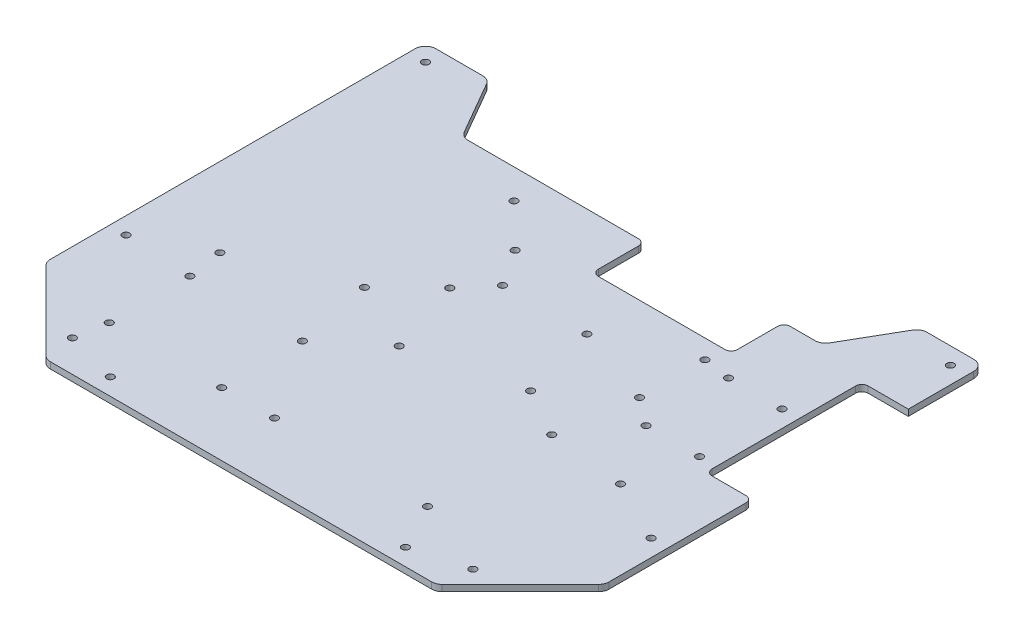
SolidWorks part; units mm, degrees
material "Acier non allié"
ref_plane "Front" through (0, 0, 0) normal (0, 0, 1) x (1, 0, 0)
ref_plane "Top" through (0, 0, 0) normal (0, 1, 0) x (1, 0, 0)
ref_plane "Right" through (0, 0, 0) normal (1, 0, 0) x (0, 0, -1)
sketch "Esquisse1" plane through (0, 0, 0) normal (0, 1, 0) x (1, 0, 0)
  line L0 (0, 0) -> (0, 190) construction
  line L1 (-92.5, 0) -> (92.5, 0)
  line L2 (92.5, 0) -> (132.5, 40)
  line L3 (132.5, 40) -> (132.5, 220)
  line L4 (132.5, 220) -> (102.5, 220)
  line L5 (102.5, 220) -> (85.1795, 190)
  line L6 (85.1795, 190) -> (-85.1795, 190)
  line L7 (-102.5, 220) -> (-85.1795, 190)
  line L8 (-132.5, 220) -> (-102.5, 220)
  line L9 (-132.5, 40) -> (-132.5, 220)
  line L10 (-92.5, 0) -> (-132.5, 40)
  dimension "D1" = 132.5
  dimension "D2" = 220
  dimension "D3" = 60
  dimension "D4" = 30
  dimension "D5" = 40
  dimension "D6" = 40
  dimension "D7" = 30
extrude "Boss.-Extru.1" add sketch "Esquisse1" along normal blind 3
fillet "Congé1" radius 5 10 edges at (92.5, 1.5, 0) (132.5, 1.5, -40) (132.5, 1.5, -220) (102.5, 1.5, -220) (85.1795, 1.5, -190) (-85.1795, 1.5, -190) (-102.5, 1.5, -220) (-132.5, 1.5, -220) (-92.5, 1.5, 0) (-132.5, 1.5, -40)
sketch "Esquisse2" plane through (0, 3, 0) normal (0, 1, 0) x (1, 0, 0)
  line L0 (0, 0) -> (0, 294.1173) construction
  line L2 (-90.4289, 0) -> (90.4289, 0) construction
  circle A0 centre (70, 8) radius 1
  circle A1 centre (124.5, 70) radius 1
  circle A2 centre (124.5, 212) radius 1
  circle A3 centre (-124.5, 212) radius 1
  circle A4 centre (-124.5, 70) radius 1
  circle A5 centre (-70, 8) radius 1
  dimension "D2" = 2
  dimension "D6" = 2
  dimension "D9" = 2
  dimension "D1" = 70
  dimension "D3" = 8
  dimension "D4" = 124.5
  dimension "D5" = 70
  dimension "D7" = 124.5
  dimension "D8" = 212
extrude "Enlèv. mat.-Extru.1" cut sketch "Esquisse2" against normal blind 3
hole_wizard "Dégagement M31" positions "Esquisse3" profile "Esquisse4" hole size "M3" standard "ISO" end condition through all
sketch "Esquisse3" plane through (0, 3, 0) normal (0, 1, 0) x (1, 0, 0)
  point P0 (70, 8)
  point P3 (-70, 8)
  point P6 (-124.5, 70)
  point P9 (-124.5, 212)
  point P12 (124.5, 212)
  point P15 (124.5, 70)
sketch "Esquisse4" plane through (70, 3, -8) normal (1, 0, 0) x (0, 0, 1)
  line L0 (0, 0) -> (0, 3)
  line L1 (0, 3) -> (1.7, 3)
  line L2 (1.7, 3) -> (1.7, 0)
  line L5 (1.7, 0) -> (0, 0)
  line L11 (0, -6.35) -> (0, 107.95) construction
  dimension "Diamètre du perçage jusqu'au prochain" = 3.4
  dimension "Profondeur du perçage jusqu'au prochain" = 3
sketch "Esquisse5" plane through (0, 3, 0) normal (0, 1, 0) x (1, 0, 0)
  line L0 (82.2927, 190) -> (-82.2927, 190) construction
  line L1 (67.5, 190) -> (1.5, 190)
  line L2 (67.5, 190) -> (67.5, 165)
  line L3 (67.5, 165) -> (1.5, 165)
  line L4 (1.5, 190) -> (1.5, 165)
  line L5 (132.5, 42.0711) -> (132.5, 215) construction
  line L6 (132.5, 184) -> (110.5, 184)
  line L7 (132.5, 184) -> (132.5, 110)
  line L8 (132.5, 110) -> (110.5, 110)
  line L9 (110.5, 184) -> (110.5, 110)
  line L10 (127.5, 220) -> (105.3868, 220) construction
  dimension "D1" = 25
  dimension "D2" = 65
  dimension "D3" = 131
  dimension "D4" = 36
  dimension "D5" = 110
  dimension "D6" = 22
extrude "Enlèv. mat.-Extru.2" cut sketch "Esquisse5" against normal through all
fillet "Congé2" radius 3 7 edges at (132.5, 1.5, -110) (110.5, 1.5, -110) (110.5, 1.5, -184) (67.5, 1.5, -190) (67.5, 1.5, -165) (1.5, 1.5, -165) (1.5, 1.5, -190)
sketch "Esquisse6" plane through (0, 3, 0) normal (0, 1, 0) x (1, 0, 0)
  line L0 (110.5, 140.5) -> (-167.6757, 140.5) construction
  line L1 (110.5, 181) -> (110.5, 113) construction
  line L2 (-90.4289, 0) -> (90.4289, 0) construction
  line L3 (110.5, 181) -> (110.5, 113) construction
  circle A0 centre (64, 156) radius 1
  circle A1 centre (-26, 156) radius 1
  circle A2 centre (-46.5, 176) radius 1
  circle A3 centre (64, 125) radius 1
  circle A4 centre (-26, 125) radius 1
  circle A5 centre (-46.5, 105) radius 1
  dimension "D4" = 2
  dimension "D6" = 2
  dimension "D10" = 2
  dimension "D1" = 140.5
  dimension "D2" = 46.5
  dimension "D3" = 15.5
  dimension "D5" = 136.5
  dimension "D7" = 15.5
  dimension "D8" = 35.5
  dimension "D9" = 157
extrude "Enlèv. mat.-Extru.3" cut sketch "Esquisse6" against normal through all
hole_wizard "Dégagement M32" positions "Esquisse7" profile "Esquisse8" hole size "M3" standard "ISO"
sketch "Esquisse7" plane through (0, 3, 0) normal (0, 1, 0) x (1, 0, 0)
  point P0 (-46.5, 105)
  point P3 (-26, 125)
  point P6 (-26, 156)
  point P9 (-46.5, 176)
  point P12 (64, 156)
  point P15 (64, 125)
sketch "Esquisse8" plane through (-46.5, 3, -105) normal (1, 0, 0) x (0, 0, 1)
  line L0 (0, 0) -> (0, 11.0215)
  line L1 (0, 11.0215) -> (1.7, 10)
  line L2 (1.7, 10) -> (1.7, 0)
  line L5 (1.7, 0) -> (0, 0)
  line L10 (0, 11.0215) -> (-1.7, 10) construction
  line L11 (0, -6.35) -> (0, 107.95) construction
  dimension "Diamètre du perçage" = 3.4
  dimension "Profondeur du perçage" = 10
  dimension "Angle de pointe" = 118
sketch "Esquisse9" plane through (0, 3, 0) normal (0, 1, 0) x (1, 0, 0)
  line L0 (132.5, 42.0711) -> (132.5, 107) construction
  line L1 (-90.4289, 0) -> (90.4289, 0) construction
  line L2 (-132.5, 215) -> (-132.5, 42.0711) construction
  line L3 (-39.16, 30) -> (-92.5, 30) construction
  line L4 (-39.16, 30) -> (-39.16, 68.24) construction
  line L5 (-39.16, 68.24) -> (-92.5, 68.24) construction
  line L6 (-92.5, 30) -> (-92.5, 68.24) construction
  line L7 (-14.16, 30) -> (-14.16, 89.182) construction
  line L8 (4.5, 165) -> (64.5, 165) construction
  line L9 (25.4456, 138.5886) -> (-14.5544, 138.5886) construction
  line L11 (113.5, 110) -> (129.5, 110) construction
  circle A0 centre (102.5, 115) radius 1
  circle A3 centre (102.5, 154.12) radius 1
  circle A6 centre (-92.5, 68.24) radius 1
  circle A7 centre (-39.16, 68.24) radius 1
  circle A8 centre (-39.16, 30) radius 1
  circle A9 centre (-92.5, 30) radius 1
  circle A10 centre (-14.16, 89.182) radius 1
  circle A11 centre (58.4456, 88.928) radius 1
  circle A12 centre (-14.16, 30) radius 1
  circle A13 centre (58.484, 30) radius 1
  circle A14 centre (-14.5544, 138.5886) radius 1
  circle A15 centre (25.4456, 138.5886) radius 1
  circle A16 centre (35.4456, 101.928) radius 1
  circle A17 centre (77.1, 115) radius 1
  circle A18 centre (77.1, 154.12) radius 1
  point P40 (77.1, 115)
  point P41 (77.1, 115)
  dimension "D2" = 2
  dimension "D4" = 2
  dimension "D17" = 2
  dimension "D18" = 2
  dimension "D19" = 2
  dimension "D20" = 2
  dimension "D21" = 2
  dimension "D22" = 2
  dimension "D23" = 2
  dimension "D24" = 2
  dimension "D32" = 2
  dimension "D33" = 2
  dimension "D34" = 2
  dimension "D11" = 2
  dimension "D12" = 2
  dimension "D5" = 30
  dimension "D6" = 30
  dimension "D7" = 5
  dimension "D8" = 25.4
  dimension "D9" = 25.4
  dimension "D10" = 39.12
  dimension "D13" = 38.24
  dimension "D14" = 53.34
  dimension "D15" = 30
  dimension "D16" = 40
  dimension "D25" = 72.606
  dimension "D26" = 72.644
  dimension "D27" = 59.182
  dimension "D28" = 58.928
  dimension "D29" = 25
  dimension "D30" = 30
  dimension "D31" = 30
  dimension "D35" = 13
  dimension "D36" = 38
  dimension "D37" = 40
  dimension "D38" = 23
  dimension "D39" = 10
  dimension "D40" = 39.12
extrude "Enlèv. mat.-Extru.4" cut sketch "Esquisse9" against normal through all
hole_wizard "Dégagement M33" positions "Esquisse10" profile "Esquisse11" hole size "M3" standard "ISO"
sketch "Esquisse10" plane through (0, 3, 0) normal (0, 1, 0) x (1, 0, 0)
  point P3 (102.5, 115)
  point P9 (102.5, 154.12)
  point P14 (77.1, 154.12)
  point P17 (77.1, 115)
sketch "Esquisse11" plane through (102.5, 3, -115) normal (1, 0, 0) x (0, 0, 1)
  line L0 (0, 0) -> (0, 11.0215)
  line L1 (0, 11.0215) -> (1.7, 10)
  line L2 (1.7, 10) -> (1.7, 0)
  line L5 (1.7, 0) -> (0, 0)
  line L10 (0, 11.0215) -> (-1.7, 10) construction
  line L11 (0, -6.35) -> (0, 107.95) construction
  dimension "Diamètre du perçage" = 3.4
  dimension "Profondeur du perçage" = 10
  dimension "Angle de pointe" = 118
sketch "Esquisse12" plane through (0, 3, 0) normal (0, 1, 0) x (1, 0, 0)
  line L2 (-90.4289, 0) -> (90.4289, 0) construction
  line L3 (95, 15) -> (-95, 15) construction
  line L4 (95, 15) -> (95, 85) construction
  line L5 (95, 85) -> (-95, 85) construction
  line L6 (-95, 15) -> (-95, 85) construction
  line L7 (132.5, 42.0711) -> (132.5, 107) construction
  circle A4 centre (-95, 85) radius 1
  circle A5 centre (95, 85) radius 1
  circle A6 centre (95, 15) radius 1
  circle A7 centre (-95, 15) radius 1
  point P6 (95, 50)
  dimension "D5" = 2
  dimension "D6" = 2
  dimension "D7" = 2
  dimension "D8" = 2
  dimension "D1" = 70
  dimension "D2" = 190
  dimension "D3" = 15
  dimension "D4" = 37.5
extrude "Enlèv. mat.-Extru.5" cut sketch "Esquisse12" against normal through all and the other way through all
hole_wizard "Dégagement M34" positions "Esquisse13" profile "Esquisse14" hole size "M3" standard "ISO"
sketch "Esquisse13" plane through (0, 3, 0) normal (0, 1, 0) x (1, 0, 0)
  point P3 (-92.5, 68.24)
  point P6 (-92.5, 30)
  point P9 (-39.16, 30)
  point P12 (-39.16, 68.24)
  point P16 (-14.16, 30)
  point P19 (58.484, 30)
  point P22 (-14.16, 89.182)
  point P25 (58.4456, 88.928)
  point P29 (35.4456, 101.928)
  point P32 (25.4456, 138.5886)
  point P35 (-14.5544, 138.5886)
sketch "Esquisse14" plane through (-92.5, 3, -68.24) normal (1, 0, 0) x (0, 0, 1)
  line L0 (0, 0) -> (0, 11.0215)
  line L1 (0, 11.0215) -> (1.7, 10)
  line L2 (1.7, 10) -> (1.7, 0)
  line L5 (1.7, 0) -> (0, 0)
  line L10 (0, 11.0215) -> (-1.7, 10) construction
  line L11 (0, -6.35) -> (0, 107.95) construction
  dimension "Diamètre du perçage" = 3.4
  dimension "Profondeur du perçage" = 10
  dimension "Angle de pointe" = 118
hole_wizard "Dégagement M35" positions "Esquisse15" profile "Esquisse16" hole size "M3" standard "ISO"
sketch "Esquisse15" plane through (0, 3, 0) normal (0, 1, 0) x (1, 0, 0)
  point P0 (-95, 15)
  point P3 (-95, 85)
  point P6 (95, 85)
  point P9 (95, 15)
sketch "Esquisse16" plane through (-95, 3, -15) normal (1, 0, 0) x (0, 0, 1)
  line L0 (0, 0) -> (0, 11.0215)
  line L1 (0, 11.0215) -> (1.7, 10)
  line L2 (1.7, 10) -> (1.7, 0)
  line L5 (1.7, 0) -> (0, 0)
  line L10 (0, 11.0215) -> (-1.7, 10) construction
  line L11 (0, -6.35) -> (0, 107.95) construction
  dimension "Diamètre du perçage" = 3.4
  dimension "Profondeur du perçage" = 10
  dimension "Angle de pointe" = 118
equation "\"WIDTH\"= 300mm'Total width of the robot"
equation "\"LENGTH\"= 220mm'Total length of the robot"
equation "\"CUT_DEPTH\"= 45mm'Depth of the cut on the edges of the plate"
equation "\"Plate_th\"= 3mm'Thickness of the plate"
equation "\"D1\"= \"Plate_th\""
